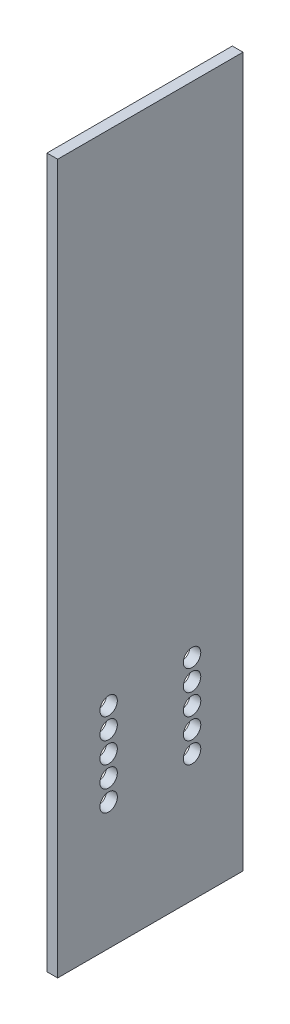
SolidWorks part; units mm, degrees
ref_plane "Front Plane" through (0, 0, 0) normal (0, 0, 1) x (1, 0, 0)
ref_plane "Top Plane" through (0, 0, 0) normal (0, 1, 0) x (1, 0, 0)
ref_plane "Right Plane" through (0, 0, 0) normal (1, 0, 0) x (0, 0, -1)
sketch "Sketch1" plane through (0, 0, 0) normal (1, 0, 0) x (0, 0, -1)
  line L1 (-28.2194, 143.51) -> (28.2194, 143.51)
  line L2 (-28.2194, 143.51) -> (-28.2194, -143.51)
  line L3 (-28.2194, -143.51) -> (28.2194, -143.51)
  line L4 (28.2194, 143.51) -> (28.2194, -143.51)
  line L5 (-28.2194, 143.51) -> (28.2194, -143.51) construction
  line L6 (-28.2194, -143.51) -> (28.2194, 143.51) construction
  point P0 (0, 0)
  dimension "D1" = 56.4388
  dimension "D2" = 287.02
extrude "Boss-Extrude1" add sketch "Sketch1" along normal blind 3.2512
sketch "Sketch2" plane through (0, 0, 0) normal (-1, 0, 0) x (0, 0, 1)
  line L0 (0, 143.51) -> (0, -143.51) construction
  line L1 (-28.2194, 143.51) -> (28.2194, 143.51) construction
  line L2 (28.2194, -143.51) -> (-28.2194, -143.51) construction
  point P7 (-12.7, -98.5012)
  point P9 (12.7, -98.5012)
  dimension "D1" = 12.7
  dimension "D2" = 45.0088
hole_wizard "#4 (0.209) Diameter Hole1" positions "Sketch3" profile "Sketch4" hole size "#4" standard "ANSI Inch" end condition through all
sketch "Sketch3" plane through (0, 0, 0) normal (-1, 0, 0) x (0, 0, 1)
  point P0 (-12.7, -98.5012)
  point P3 (12.7, -98.5012)
sketch "Sketch4" plane through (0, -98.5012, -12.7) normal (0, 1, 0) x (0, 0, 1)
  line L0 (0, 0) -> (0, 3.2512)
  line L1 (0, 3.2512) -> (2.6543, 3.2512)
  line L2 (2.6543, 3.2512) -> (2.6543, 0)
  line L5 (2.6543, 0) -> (0, 0)
  line L11 (0, -6.35) -> (0, 107.95) construction
  dimension "Thru Hole Dia." = 5.3086
  dimension "Thru Hole Depth" = 3.2512
sketch "Sketch5" plane through (0, 0, 0) normal (-1, 0, 0) x (0, 0, 1)
  line L0 (28.2194, 143.51) -> (28.2194, -143.51) construction
  line L1 (-28.2194, 143.51) -> (28.2194, 143.51)
  line L2 (-28.2194, 143.51) -> (-28.2194, 72.39)
  line L3 (-28.2194, 72.39) -> (28.2194, 72.39)
  line L4 (28.2194, 143.51) -> (28.2194, 72.39)
  dimension "D1" = 71.12
extrude "Cut-Extrude1" cut sketch "Sketch5" against normal up to next
pattern_linear "LPattern1" count 4 spacing 6.35 along (0, 1, 0) count 2 spacing 6.35 along (0, -1, 0) of "#4 (0.209) Diameter Hole1" pattern seed only yes
equation "\"motor offset\"=6mm"
equation "\"thickness0.25\"=0.225in"
equation "\"thickness0.125\"=0.122in"
equation "\"thickness_acrylic0.1\"= 0.1in"
equation "\"D1@Sketch1\"=\"thickness_acrylic0.1\"+\"thickness0.125\"+2"
equation "\"D2@Sketch2\"=\"thickness0.125\"+0.5+1.15"
